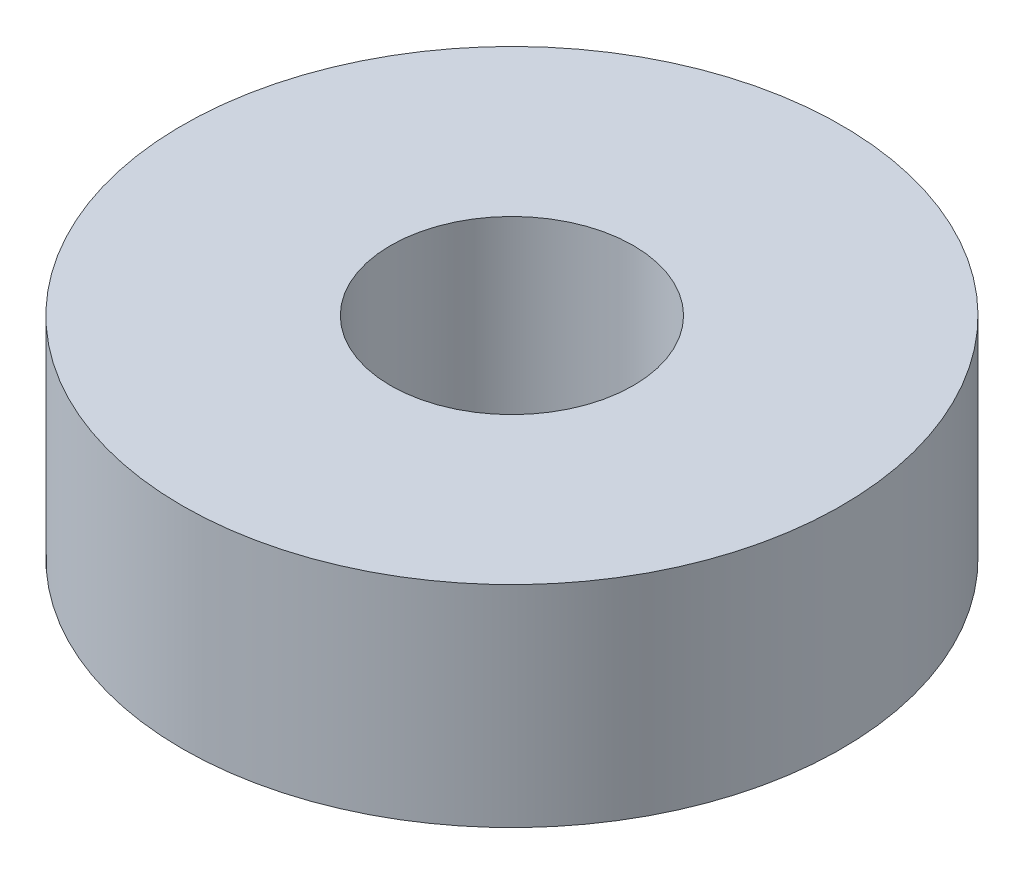
SolidWorks part; units mm, degrees
ref_plane "Front Plane" through (0, 0, 0) normal (0, 0, 1) x (1, 0, 0)
ref_plane "Top Plane" through (0, 0, 0) normal (0, 1, 0) x (1, 0, 0)
ref_plane "Right Plane" through (0, 0, 0) normal (1, 0, 0) x (0, 0, -1)
sketch "Sketch1" plane through (0, 0, 0) normal (0, 1, 0) x (1, 0, 0)
  circle A0 centre (0, 0) radius 10.9625
  circle A1 centre (0, 0) radius 4.0375
  dimension "D1" = 21.925
  dimension "D2" = 8.075
extrude "Boss-Extrude1" add sketch "Sketch1" along normal blind 7
